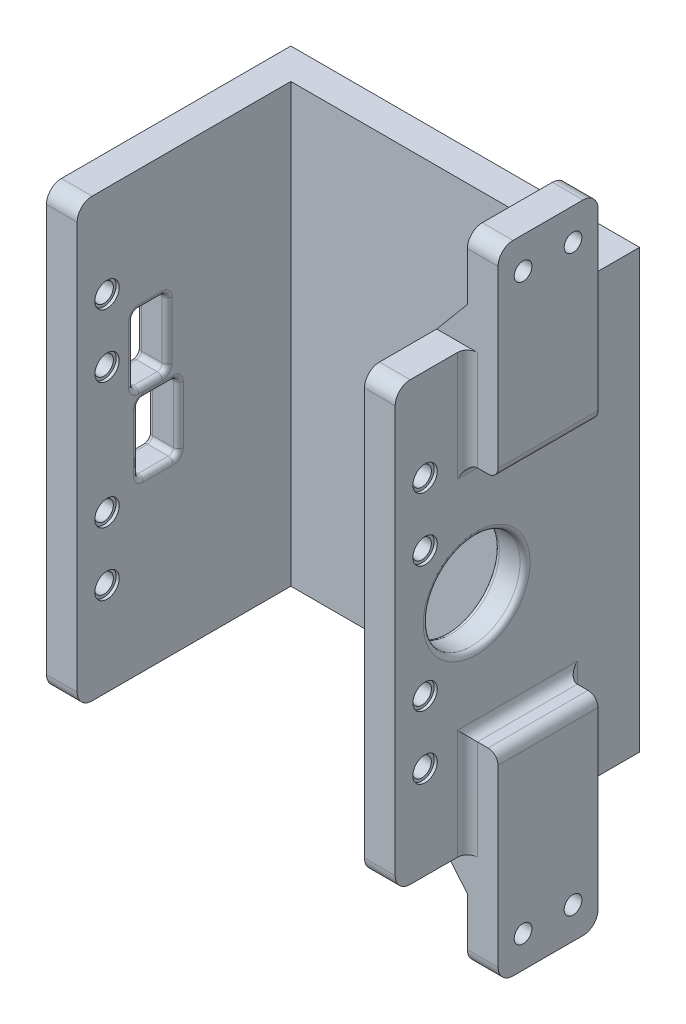
SolidWorks part; units mm, degrees
ref_plane "Front Plane" through (0, 0, 0) normal (0, 0, 1) x (1, 0, 0)
ref_plane "Top Plane" through (0, 0, 0) normal (0, 1, 0) x (1, 0, 0)
ref_plane "Right Plane" through (0, 0, 0) normal (1, 0, 0) x (0, 0, -1)
sketch "Sketch1" plane through (0, 0, 0) normal (1, 0, 0) x (0, 0, -1)
  line L1 (0, 0) -> (55.1, 0)
  line L2 (0, 0) -> (0, 111.1)
  line L3 (0, 111.1) -> (55.1, 111.1)
  line L4 (55.1, 0) -> (55.1, 111.1)
  dimension "D1" = 55.1
  dimension "D2" = 111.1
extrude "Boss-Extrude1" add sketch "Sketch1" along normal blind 7.8
sketch "Sketch2" plane through (0, 0, 0) normal (-1, 0, 0) x (0, 0, 1)
  line L0 (0, 111.1) -> (-47.3, 111.1) construction
  line L1 (-55.1, 111.1) -> (0, 111.1) construction
  line L3 (-47.3, 111.1) -> (-55.1, 111.1)
  line L4 (-47.3, 111.1) -> (-47.3, 0)
  line L5 (-47.3, 0) -> (-55.1, 0)
  line L6 (-55.1, 111.1) -> (-55.1, 0)
  dimension "D1" = 7.8
extrude "Boss-Extrude2" add sketch "Sketch2" along normal blind 73.025 contours L4 L3 L6 L5
sketch "Sketch4" plane through (-73.025, 0, 0) normal (-1, 0, 0) x (0, 0, 1)
  line L1 (-55.1, 111.1) -> (0, 111.1)
  line L2 (-55.1, 111.1) -> (-55.1, 0)
  line L3 (-55.1, 0) -> (0, 0)
  line L4 (0, 111.1) -> (0, 0)
extrude "Boss-Extrude3" add sketch "Sketch4" along normal blind 7.8 contours L2 L1 L4 L3
ref_plane "Plane1" through (-36.5125, 0, 0) normal (-1, 0, 0) x (0, 0, 1)
sketch "Sketch7" plane through (0, 0, 0) normal (0, 0, 1) x (1, 0, 0)
  line L4 (0, 0) -> (7.8, 0)
  line L5 (7.8, 0) -> (7.8, 111.1)
  line L6 (7.8, 111.1) -> (0, 111.1)
  line L7 (0, 111.1) -> (0, 0)
  line L8 (0, 0) -> (7.8, 0)
  line L10 (7.8, 111.1) -> (0, 111.1)
  line L11 (0, 111.1) -> (0, 0)
  line L16 (7.8, 0) -> (7.8, 111.1)
  dimension "D1" = 0
extrude "Boss-Extrude4" add sketch "Sketch7" along normal blind 7 contours L8 L16 L10 L11
sketch "Sketch8" plane through (7.8, 0, 0) normal (1, 0, 0) x (0, 0, -1)
  line L1 (-7, 0) -> (-7, 111.1) construction
  line L2 (-7, 0) -> (55.1, 0) construction
  line L3 (0.6, 30.1777) -> (0.6, 16.5296) construction
  circle A0 centre (0.6, 23.6) radius 3.1
  circle A1 centre (0.6, 23.6) radius 2.4
  circle A2 centre (0.6, 39.6) radius 3.1
  circle A3 centre (0.6, 39.6) radius 2.4
  circle A4 centre (0.6, 87.6) radius 3.1
  circle A5 centre (0.6, 87.6) radius 2.4
  circle A6 centre (0.6, 71.6) radius 3.1
  circle A7 centre (0.6, 71.6) radius 2.4
  dimension "D1" = 6.2
  dimension "D2" = 4.8
  dimension "D5" = 6.2
  dimension "D6" = 4.8
  dimension "D3" = 23.6
  dimension "D4" = 16
  dimension "D7" = 16
  dimension "D8" = 32
  dimension "D9" = 7.6
extrude "Cut-Extrude4" cut sketch "Sketch8" against normal blind 12.7 contours A5 | A7 | A3 | A1 L3 | L3 A1 region at (7.8, 23.6, -1.6186) region at (7.8, 23.6, 0.4186) region at (7.8, 39.6, -0.6) region at (7.8, 87.6, -0.6) region at (7.8, 71.6, -0.6)
extrude "Cut-Extrude5" cut sketch "Sketch8<4>" against normal blind 0.8 contours A4 | A6 | A2 | A0
sketch "Sketch8<4>" plane through (7.8, 0, 0) normal (1, 0, 0) x (0, 0, -1) same geometry as "Sketch8"
sketch "Sketch9" plane through (0, 0, 7) normal (0, 0, 1) x (1, 0, 0)
  line L0 (3.9, 0) -> (3.9, 111.1) construction
  line L1 (0, 0) -> (7.8, 0) construction
  line L2 (7.8, 111.1) -> (0, 111.1) construction
ref_plane "Plane2" through (3.9, 0, 0) normal (1, 0, 0) x (0, 0, -1)
mirror "Mirror1" about plane through (3.9, 0, 0) normal (1, 0, 0) of "Cut-Extrude5"
mirror "Mirror2" about plane through (-36.5125, 0, 0) normal (-1, 0, 0) of "Cut-Extrude4", "Boss-Extrude4", "Mirror1", "Cut-Extrude5"
sketch "Sketch10" plane through (7.8, 0, 0) normal (1, 0, 0) x (0, 0, -1)
  line L1 (-7, 0) -> (55.1, 0) construction
  line L2 (-7, 0) -> (-7, 111.1) construction
  circle A0 centre (13.7, 55.7) radius 12.3
  dimension "D1" = 24.6
  dimension "D2" = 20.7
  dimension "D3" = 55.7
extrude "Cut-Extrude7" cut sketch "Sketch10" against normal up to surface (7.8 mm away) up to face at (0, 87.6, -3.7)
sketch "Sketch11" plane through (-80.825, 0, 0) normal (-1, 0, 0) x (0, 0, 1)
  line L1 (-14.6, 78.8) -> (-8.6, 78.8) construction
  line L2 (-14.6, 78.8) -> (-14.6, 64.2) construction
  line L3 (-14.6, 64.2) -> (-8.6, 64.2) construction
  line L4 (-8.6, 78.8) -> (-8.6, 64.2) construction
  line L5 (-17.435, 58.8) -> (-9.8, 58.8) construction
  line L6 (-17.435, 58.8) -> (-17.435, 44.2) construction
  line L7 (-17.435, 44.2) -> (-9.8, 44.2) construction
  line L8 (-9.8, 58.8) -> (-9.8, 44.2) construction
  line L9 (-55.1, 0) -> (7, 0) construction
  line L10 (-15.87, 80.07) -> (-7.33, 80.07)
  line L11 (-7.33, 80.07) -> (-7.33, 62.93)
  line L12 (-15.87, 62.93) -> (-7.33, 62.93)
  line L13 (-15.87, 80.07) -> (-15.87, 62.93)
  line L14 (-8.53, 60.07) -> (-8.53, 42.93)
  line L15 (-18.705, 42.93) -> (-8.53, 42.93)
  line L16 (-18.705, 60.07) -> (-18.705, 42.93)
  line L17 (-18.705, 60.07) -> (-8.53, 60.07)
  line L18 (7, 0) -> (7, 111.1) construction
  dimension "D1" = 14.6
  dimension "D2" = 6
  dimension "D3" = 15.6
  dimension "D4" = 64.2
  dimension "D5" = 14.6
  dimension "D6" = 7.635
  dimension "D7" = 16.8
  dimension "D8" = 44.2
  dimension "D9" = 1.27
  dimension "D10" = 1.27
extrude "Cut-Extrude8" cut sketch "Sketch11" against normal up to surface (7.8 mm away) contours L10 L11 L12 L13 | L14 L15 L16 L17 up to face at (-73.025, 87.6, -3.7)
fillet "Fillet1" radius 1.27 26 edges at (-73.025, 51.5, -18.705) (-80.825, 51.5, -18.705) (-73.025, 42.93, -13.6175) (-80.825, 42.93, -13.6175) (-76.925, 42.93, -18.705) (-80.825, 51.5, -8.53) (-76.925, 42.93, -8.53) (-73.025, 51.5, -8.53) (-76.925, 60.07, -18.705) (-80.825, 60.07, -13.6175) (-76.925, 60.07, -8.53) (-73.025, 60.07, -13.6175) (-73.025, 62.93, -11.6) (-80.825, 62.93, -11.6) (-80.825, 71.5, -7.33) (-76.925, 62.93, -7.33) (-73.025, 71.5, -7.33) (-80.825, 80.07, -11.6) (-76.925, 80.07, -7.33) (-73.025, 80.07, -11.6) (-73.025, 71.5, -15.87) (-76.925, 62.93, -15.87) (-80.825, 71.5, -15.87) (-76.925, 80.07, -15.87) (0, 55.7, -1.4) (7.8, 55.7, -26)
sketch "Sketch12" plane through (0, 111.1, 0) normal (0, 1, 0) x (1, 0, 0)
  line L0 (7.8, 55.1) -> (7.8, -7) construction
  line L1 (7.8, 36.75) -> (15.6, 36.75)
  line L2 (7.8, 36.75) -> (7.8, 11.35)
  line L3 (7.8, 11.35) -> (15.6, 11.35)
  line L4 (15.6, 36.75) -> (15.6, 11.35)
  point P6 (7.8, 24.05)
  point P7 (7.8, 24.05)
  dimension "D1" = 25.4
  dimension "D2" = 7.8
extrude "Boss-Extrude5" add sketch "Sketch12" along normal mid plane 50.8
sketch "Sketch13" plane through (7.8, 0, 0) normal (1, 0, 0) x (0, 0, -1)
  line L0 (29.7, 111.1) -> (29.7, 0) construction
  line L1 (-7, 0) -> (55.1, 0) construction
  line L2 (55.1, 0) -> (55.1, 111.1) construction
  point P5 (29.7, 55.55)
  dimension "D1" = 25.4
ref_plane "Plane3" through (0, 55.55, 0) normal (0, 1, 0) x (1, 0, 0)
sketch "Sketch14" plane through (0, 0, 0) normal (-1, 0, 0) x (0, 0, 1)
  line L0 (-36.75, 136.5) -> (-11.35, 136.5) construction
  line L1 (-55.1, 111.1) -> (7, 111.1) construction
  line L2 (-36.75, 136.5) -> (-36.75, 111.1) construction
  circle A0 centre (-30.4, 123.8) radius 1.5875
  circle A1 centre (-17.7, 123.8) radius 1.5875
  dimension "D1" = 3.175
  dimension "D2" = 3.175
  dimension "D3" = 12.7
  dimension "D4" = 12.7
  dimension "D5" = 12.7
  dimension "D6" = 6.35
mirror "Mirror6" about plane through (0, 55.55, 0) normal (0, 1, 0) of "Boss-Extrude5"
chamfer "Chamfer2" distance 7.8 angle 50 2 edges at (7.8, 111.1, -24.05) (7.8, 0, -24.05) first distance on face at (-27.65, 111.1, -22.49) first distance on face at (-27.65, 0, -22.49)
fillet "Fillet3" radius 3.81 8 edges at (-76.925, 0, 7) (-76.925, 111.1, 7) (3.9, 111.1, 7) (3.9, 0, 7) (11.7, -25.4, -36.75) (11.7, -25.4, -11.35) (11.7, 136.5, -36.75) (11.7, 136.5, -11.35)
fillet "Fillet4" radius 2.54 8 edges at (7.8, 98.4, -36.75) (7.8, 98.4, -11.35) (7.8, 85.7, -24.05) (15.6, 85.7, -24.05) (15.6, 25.4, -24.05) (7.8, 12.7, -11.35) (7.8, 25.4, -24.05) (7.8, 12.7, -36.75)
hole_wizard "#8 Clearance Hole1" positions "Sketch15" profile "Sketch16" hole size "#8" standard "ANSI Inch" end condition through all
sketch "Sketch15" plane through (7.8, 0, 0) normal (-1, 0, 0) x (0, 0, 1)
  line L0 (-24.05, 136.5) -> (-24.05, 120.3957) construction
  line L1 (-32.94, 136.5) -> (-15.16, 136.5) construction
  line L2 (-36.75, 120.3957) -> (-11.35, 120.3957) construction
  line L4 (-36.75, 132.69) -> (-36.75, 120.3957) construction
  line L5 (-11.35, 132.69) -> (-11.35, 120.3957) construction
  point P0 (-30.4, 128.4478)
  point P3 (-17.7, 128.4478)
  point P15 (0, 0)
  point P16 (0, 0)
  point P17 (0, 0)
  point P18 (0, 0)
  point P19 (-24.05, 128.4478)
  dimension "D1" = 6.35
  dimension "D2" = 6.35
sketch "Sketch16" plane through (7.8, 128.4478, -30.4) normal (0, 1, 0) x (0, 0, 1)
  line L0 (0, 0) -> (0, 7.8)
  line L1 (0, 7.8) -> (2.2479, 7.8)
  line L2 (2.2479, 7.8) -> (2.2479, 0)
  line L5 (2.2479, 0) -> (0, 0)
  line L11 (0, -6.35) -> (0, 107.95) construction
  dimension "Thru Hole Dia." = 4.4958
  dimension "Thru Hole Depth" = 7.8
mirror "Mirror7" about plane through (0, 55.55, 0) normal (0, 1, 0) of "#8 Clearance Hole1"
